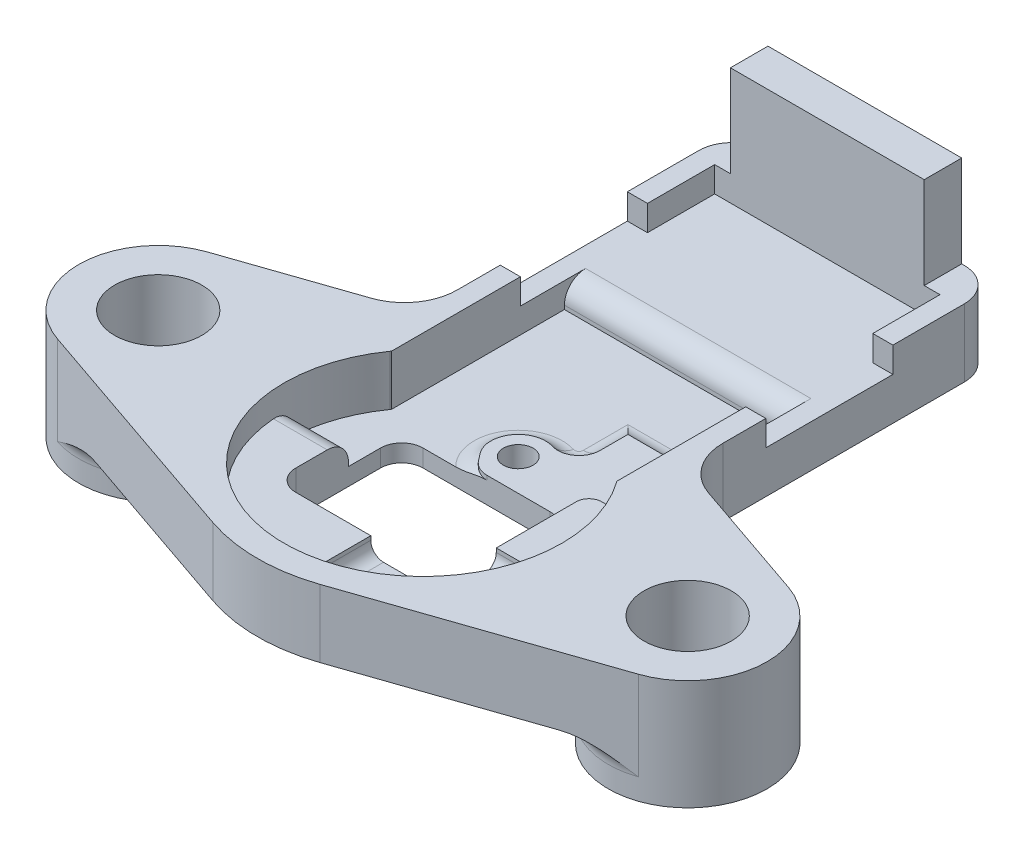
SolidWorks part; units mm, degrees
ref_plane "Front Plane" through (0, 0, 0) normal (0, 0, 1) x (1, 0, 0)
ref_plane "Top Plane" through (0, 0, 0) normal (0, 1, 0) x (1, 0, 0)
ref_plane "Right Plane" through (0, 0, 0) normal (1, 0, 0) x (0, 0, -1)
sketch "Sketch1" plane through (0, 0, 0) normal (0, -1, 0) x (1, 0, 0)
  line L6 (6.3754, -15.4686) -> (6.3754, -6.1404)
  line L7 (-6.3754, -15.4686) -> (6.3754, -15.4686)
  line L8 (-6.3754, -6.1404) -> (-6.3754, -15.4686)
  line L20 (17.4219, 4.5043) -> (3.2216, 9.3809)
  line L21 (-3.2216, 9.3809) -> (-17.4219, 4.5043)
  line L22 (-17.4219, -4.5043) -> (-10.1067, -7.0165)
  line L23 (-7.9629, -10.0193) -> (-7.9629, -14.7701)
  line L24 (-5.6769, -17.0561) -> (5.6769, -17.0561)
  line L25 (7.9629, -14.7701) -> (7.9629, -10.0193)
  line L26 (10.1067, -7.0165) -> (17.4219, -4.5043)
  circle A2 centre (15.875, 0) radius 2.6162
  arc A6 (6.7965, -4.8183) -> (-6.7965, -4.8183) centre (0, 0) ccw
  arc A7 (6.7965, -4.8183) -> (6.3754, -6.1404) centre (8.6614, -6.1404) ccw
  arc A8 (-6.3754, -6.1404) -> (-6.7965, -4.8183) centre (-8.6614, -6.1404) ccw
  circle A10 centre (-15.875, 0) radius 2.6162
  arc A24 (3.2216, 9.3809) -> (-3.2216, 9.3809) centre (0, 0) ccw
  arc A25 (-17.4219, 4.5043) -> (-17.4219, -4.5043) centre (-15.875, 0) ccw
  arc A26 (-7.9629, -10.0193) -> (-10.1067, -7.0165) centre (-11.1379, -10.0193) ccw
  arc A27 (-7.9629, -14.7701) -> (-5.6769, -17.0561) centre (-5.6769, -14.7701) ccw
  arc A28 (5.6769, -17.0561) -> (7.9629, -14.7701) centre (5.6769, -14.7701) ccw
  arc A29 (10.1067, -7.0165) -> (7.9629, -10.0193) centre (11.1379, -10.0193) ccw
  arc A30 (17.4219, -4.5043) -> (17.4219, 4.5043) centre (15.875, 0) ccw
extrude "Boss-Extrude1" add sketch "Sketch1" along normal blind 6.604
sketch "Sketch2" plane through (0, -6.604, 0) normal (0, -1, 0) x (1, 0, 0)
  line L3 (6.3754, -15.4686) -> (6.3754, -6.1404)
  line L4 (-6.3754, -15.4686) -> (6.3754, -15.4686)
  line L5 (-6.3754, -6.1404) -> (-6.3754, -15.4686)
  line L6 (6.3754, -15.4686) -> (6.3754, -6.1404)
  line L7 (-6.3754, -15.4686) -> (6.3754, -15.4686)
  line L8 (-6.3754, -6.1404) -> (-6.3754, -15.4686)
  arc A3 (6.7965, -4.8183) -> (-6.7965, -4.8183) centre (0, 0) ccw
  arc A4 (6.7965, -4.8183) -> (6.3754, -6.1404) centre (8.6614, -6.1404) ccw
  arc A5 (-6.3754, -6.1404) -> (-6.7965, -4.8183) centre (-8.6614, -6.1404) ccw
  arc A6 (6.7965, -4.8183) -> (-6.7965, -4.8183) centre (0, 0) ccw
  arc A7 (6.7965, -4.8183) -> (6.3754, -6.1404) centre (8.6614, -6.1404) ccw
  arc A8 (-6.3754, -6.1404) -> (-6.7965, -4.8183) centre (-8.6614, -6.1404) ccw
  dimension "D1" = 0
extrude "Boss-Extrude2" add sketch "Sketch2" against normal blind 5.08
sketch "Sketch3" plane through (0, -6.604, 0) normal (0, -1, 0) x (1, 0, 0)
  line L7 (17.4219, 4.5043) -> (3.2216, 9.3809)
  line L8 (-3.2216, 9.3809) -> (-17.4219, 4.5043)
  line L9 (-17.4219, -4.5043) -> (-10.1067, -7.0165)
  line L10 (-7.9629, -10.0193) -> (-7.9629, -14.7701)
  line L11 (-5.6769, -17.0561) -> (5.6769, -17.0561)
  line L12 (7.9629, -14.7701) -> (7.9629, -10.0193)
  line L13 (10.1067, -7.0165) -> (17.4219, -4.5043)
  line L14 (17.4219, 4.5043) -> (3.2216, 9.3809)
  line L15 (-3.2216, 9.3809) -> (-17.4219, 4.5043)
  line L16 (-17.4219, -4.5043) -> (-10.1067, -7.0165)
  line L17 (-7.9629, -10.0193) -> (-7.9629, -14.7701)
  line L18 (-5.6769, -17.0561) -> (5.6769, -17.0561)
  line L19 (7.9629, -14.7701) -> (7.9629, -10.0193)
  line L20 (10.1067, -7.0165) -> (17.4219, -4.5043)
  circle A0 centre (-15.875, 0) radius 4.7625
  circle A1 centre (15.875, 0) radius 2.6162
  circle A2 centre (15.875, 0) radius 2.6162
  circle A3 centre (-15.875, 0) radius 2.6162
  circle A4 centre (-15.875, 0) radius 2.6162
  circle A5 centre (15.875, 0) radius 4.7625
  arc A6 (17.4219, -4.5043) -> (17.4219, 4.5043) centre (15.875, 0) ccw construction
  arc A7 (-17.4219, 4.5043) -> (-17.4219, -4.5043) centre (-15.875, 0) ccw construction
  arc A8 (17.4219, -4.5043) -> (17.4219, 4.5043) centre (15.875, 0) ccw
  arc A9 (-17.4219, 4.5043) -> (-17.4219, -4.5043) centre (-15.875, 0) ccw
  arc A17 (17.4219, -4.5043) -> (17.4219, 4.5043) centre (15.875, 0) ccw
  arc A18 (3.2216, 9.3809) -> (-3.2216, 9.3809) centre (0, 0) ccw
  arc A19 (-17.4219, 4.5043) -> (-17.4219, -4.5043) centre (-15.875, 0) ccw
  arc A20 (-7.9629, -10.0193) -> (-10.1067, -7.0165) centre (-11.1379, -10.0193) ccw
  arc A21 (-7.9629, -14.7701) -> (-5.6769, -17.0561) centre (-5.6769, -14.7701) ccw
  arc A22 (5.6769, -17.0561) -> (7.9629, -14.7701) centre (5.6769, -14.7701) ccw
  arc A23 (10.1067, -7.0165) -> (7.9629, -10.0193) centre (11.1379, -10.0193) ccw
  arc A24 (17.4219, -4.5043) -> (17.4219, 4.5043) centre (15.875, 0) ccw
  arc A25 (3.2216, 9.3809) -> (-3.2216, 9.3809) centre (0, 0) ccw
  arc A26 (-17.4219, 4.5043) -> (-17.4219, -4.5043) centre (-15.875, 0) ccw
  arc A27 (-7.9629, -10.0193) -> (-10.1067, -7.0165) centre (-11.1379, -10.0193) ccw
  arc A28 (-7.9629, -14.7701) -> (-5.6769, -17.0561) centre (-5.6769, -14.7701) ccw
  arc A29 (5.6769, -17.0561) -> (7.9629, -14.7701) centre (5.6769, -14.7701) ccw
  arc A30 (10.1067, -7.0165) -> (7.9629, -10.0193) centre (11.1379, -10.0193) ccw
  line M19 (17.4219, 4.5043) -> (3.2216, 9.3809)
  arc M20 (3.2216, 9.3809) -> (-3.2216, 9.3809) centre (0, 0) ccw
  line M21 (-3.2216, 9.3809) -> (-17.4219, 4.5043)
  line M23 (-17.4219, -4.5043) -> (-10.1067, -7.0165)
  arc M24 (-10.1067, -7.0165) -> (-7.9629, -10.0193) centre (-11.1379, -10.0193) cw
  line M25 (-7.9629, -10.0193) -> (-7.9629, -14.7701)
  arc M26 (-7.9629, -14.7701) -> (-5.6769, -17.0561) centre (-5.6769, -14.7701) ccw
  line M27 (-5.6769, -17.0561) -> (5.6769, -17.0561)
  arc M28 (5.6769, -17.0561) -> (7.9629, -14.7701) centre (5.6769, -14.7701) ccw
  line M29 (7.9629, -14.7701) -> (7.9629, -10.0193)
  arc M30 (7.9629, -10.0193) -> (10.1067, -7.0165) centre (11.1379, -10.0193) cw
  line M31 (10.1067, -7.0165) -> (17.4219, -4.5043)
  dimension "D1" = 0
  dimension "D2" = 0
  dimension "D3" = 0
extrude "Cut-Extrude1" cut sketch "Sketch3" against normal blind 2.54 contours A5 A0 M19 M20 M21 M23 M24 M25 M26 M27 M28 M29 M30 M31 region at (0, -6.604, -2.9981)
sketch "Sketch5" plane through (0, -6.604, 0) normal (0, -1, 0) x (1, 0, 0)
  line L0 (-15.875, 0) -> (15.875, 0) construction
  circle A0 centre (0, 0) radius 12.446
  circle A1 centre (15.875, 0) radius 2.6162
  circle A2 centre (15.875, 0) radius 2.6162
  circle A3 centre (-15.875, 0) radius 2.6162
  circle A4 centre (-15.875, 0) radius 2.6162
  dimension "D3" = 24.892
  dimension "D1" = 0
  dimension "D2" = 0
extrude "Cut-Extrude2" cut sketch "Sketch5" against normal blind 1.6002
sketch "Sketch6" plane through (0, -6.604, 0) normal (0, -1, 0) x (1, 0, 0)
  line L0 (-15.875, 0) -> (15.875, 0) construction
  circle A0 centre (0, 0) radius 3.302
  circle A1 centre (15.875, 0) radius 2.6162
  circle A2 centre (15.875, 0) radius 2.6162
  circle A3 centre (-15.875, 0) radius 2.6162
  circle A4 centre (-15.875, 0) radius 2.6162
  dimension "D3" = 6.604
  dimension "D1" = 0
  dimension "D2" = 0
extrude "Cut-Extrude3" cut sketch "Sketch6" against normal through all contours A0
sketch "Sketch8" plane through (0, 0, 0) normal (0, 1, 0) x (1, 0, 0)
  line L0 (-7.9629, 10.0193) -> (-7.9629, 14.7701) construction
  line L1 (-7.9629, 11.8189) -> (7.9629, 11.8189)
  line L2 (-7.9629, 11.8189) -> (-7.9629, 19.6086)
  line L3 (-7.9629, 19.6086) -> (7.9629, 19.6086)
  line L4 (7.9629, 11.8189) -> (7.9629, 19.6086)
extrude "Cut-Extrude4" cut sketch "Sketch8" against normal through all
sketch "Sketch9" plane through (0, 0, -11.8189) normal (0, 0, -1) x (-1, 0, 0)
  line L8 (6.3754, 0) -> (6.3754, -1.524)
  line L9 (6.3754, -1.524) -> (-6.3754, -1.524)
  line L10 (-6.3754, -1.524) -> (-6.3754, 0)
  line L11 (-6.3754, 0) -> (-7.9629, 0)
  line L12 (-7.9629, 0) -> (-7.9629, -4.064)
  line L13 (-7.9629, -4.064) -> (7.9629, -4.064)
  line L14 (7.9629, -4.064) -> (7.9629, 0)
  line L15 (7.9629, 0) -> (6.3754, 0)
  line L16 (6.3754, 0) -> (6.3754, -1.524)
  line L17 (6.3754, -1.524) -> (-6.3754, -1.524)
  line L18 (-6.3754, -1.524) -> (-6.3754, 0)
  line L19 (-6.3754, 0) -> (-7.9629, 0)
  line L20 (-7.9629, 0) -> (-7.9629, -4.064)
  line L21 (-7.9629, -4.064) -> (7.9629, -4.064)
  line L22 (7.9629, -4.064) -> (7.9629, 0)
  line L23 (7.9629, 0) -> (6.3754, 0)
  dimension "D1" = 0
extrude "Boss-Extrude3" add sketch "Sketch9" along normal blind 25.4
sketch "Sketch11" plane through (0, 0, 0) normal (0, 1, 0) x (1, 0, 0)
  line L0 (-7.9629, 10.0193) -> (-7.9629, 37.2189) construction
  line L1 (7.9629, 37.2189) -> (-7.9629, 37.2189)
  line L2 (7.9629, 37.2189) -> (7.9629, 23.5)
  line L3 (7.9629, 23.5) -> (-7.9629, 23.5)
  line L4 (-7.9629, 37.2189) -> (-7.9629, 23.5)
  point P7 (0, 23.5)
  dimension "D1" = 23.5
extrude "Cut-Extrude5" cut sketch "Sketch11" against normal through all
sketch "Sketch12" plane through (0, 0, -23.5) normal (0, 0, -1) x (-1, 0, 0)
  line L1 (-7.9629, 0) -> (7.9629, 0)
  line L2 (-7.9629, 0) -> (-7.9629, -4.064)
  line L3 (-7.9629, -4.064) -> (7.9629, -4.064)
  line L4 (7.9629, 0) -> (7.9629, -4.064)
extrude "Boss-Extrude4" add sketch "Sketch12" along normal blind 2
sketch "Sketch13" plane through (0, -1.524, 0) normal (0, 1, 0) x (1, 0, 0)
  line L0 (0, 0) -> (0, 5.715) construction
  circle A0 centre (0, 5.715) radius 0.889
  dimension "D1" = 1.778
  dimension "D2" = 5.715
extrude "Cut-Extrude6" cut sketch "Sketch13" against normal through all
sketch "Sketch14" plane through (0, 0, 0) normal (0, 1, 0) x (1, 0, 0)
  line L0 (0, 0) -> (0, 15.1) construction
  line L1 (-7.9629, 10.0193) -> (-7.9629, 25.5) construction
  line L2 (-7.9629, 12.6) -> (7.9629, 12.6)
  line L3 (-7.9629, 12.6) -> (-7.9629, 20.22)
  line L4 (-7.9629, 20.22) -> (7.9629, 20.22)
  line L5 (7.9629, 12.6) -> (7.9629, 20.22)
  line L6 (7.9629, 25.5) -> (7.9629, 10.0193) construction
  circle A1 centre (0, 0) radius 3.302
  circle A4 centre (0, 0) radius 3.302 construction
  line M5 (7.9629, 10.0193) -> (7.9629, 25.5)
  line M7 (-7.9629, 25.5) -> (-7.9629, 10.0193)
  line M18 (6.3754, 23.5) -> (6.3754, 6.1404)
  line M22 (-6.3754, 6.1404) -> (-6.3754, 23.5)
  dimension "D2" = 15.1
  dimension "D3" = 2.5
  dimension "D4" = 7.62
  dimension "D1" = 0
extrude "Cut-Extrude8" cut sketch "Sketch14" against normal up to surface (1.524 mm away) contours L4 L2 M22 M18 | L4 L2 M7 M22 | L4 L2 M18 M5 region at (-7.1691, 0, -16.41) region at (0, 0, -16.41) region at (7.1692, 0, -16.41) up to face at (0, -1.524, -4.826)
sketch "Sketch15" plane through (0, -1.524, 0) normal (0, 1, 0) x (1, 0, 0)
  line L1 (5.08, 3.81) -> (-5.08, 3.81)
  line L2 (5.08, 3.81) -> (5.08, -3.81)
  line L3 (5.08, -3.81) -> (-5.08, -3.81)
  line L4 (-5.08, 3.81) -> (-5.08, -3.81)
  line L5 (5.08, 3.81) -> (-5.08, -3.81) construction
  line L6 (5.08, -3.81) -> (-5.08, 3.81) construction
  point P0 (0, 0)
  dimension "D1" = 7.62
  dimension "D2" = 10.16
extrude "Cut-Extrude9" cut sketch "Sketch15" against normal through all
sketch "Sketch19" plane through (0, 0, 0) normal (0, 1, 0) x (1, 0, 0)
  line L0 (-6.3754, 23.5) -> (6.3754, 23.5) construction
  line L1 (6.7564, 2.54) -> (-6.7564, 2.54)
  line L2 (6.7564, 2.54) -> (6.7564, 23.5)
  line L3 (6.7564, 23.5) -> (-6.7564, 23.5)
  line L4 (-6.7564, 2.54) -> (-6.7564, 23.5)
  line L5 (-6.3754, 6.1404) -> (-6.3754, 12.6) construction
  point P6 (0, 2.54)
  dimension "D1" = 0.381
  dimension "D2" = 2.54
extrude "Cut-Extrude13" cut sketch "Sketch19" against normal up to surface (1.524 mm away) up to face at (0, -1.524, 0)
sketch "Sketch16" plane through (0, -1.524, 0) normal (0, 1, 0) x (1, 0, 0)
  line L0 (5.08, 3.81) -> (-5.08, 3.81) construction
  line L1 (-6.7564, 3.81) -> (2.1336, 3.81)
  line L2 (-6.7564, 3.81) -> (-6.7564, 15.24)
  line L3 (-6.7564, 15.24) -> (2.1336, 15.24)
  line L4 (2.1336, 3.81) -> (2.1336, 15.24)
  line L8 (2.1336, 15.24) -> (6.7564, 15.24)
  line L9 (2.1336, 15.24) -> (2.1336, 10.16)
  line L10 (2.1336, 10.16) -> (6.7564, 10.16)
  line L11 (6.7564, 15.24) -> (6.7564, 10.16)
  line L12 (-6.7564, 12.6) -> (-6.7564, 4.8768) construction
  line L13 (6.7564, 4.8768) -> (6.7564, 12.6) construction
  line M7 (-5.08, 3.81) -> (5.08, 3.81)
  circle M9 centre (0, 5.715) radius 0.889
  dimension "D1" = 8.89
  dimension "D2" = 11.43
  dimension "D3" = 5.08
extrude "Cut-Extrude10" cut sketch "Sketch16" against normal blind 1.5 contours L4 L3 L2 L1 M7 M9 | L11 L8 L4 L10 region at (-2.3693, -1.524, -9.6204) region at (4.445, -1.524, -12.7)
sketch "Sketch18" plane through (0, -1.524, 0) normal (0, 1, 0) x (1, 0, 0)
  line L1 (2.1336, 10.16) -> (6.7564, 10.16)
  line L2 (2.1336, 10.16) -> (2.1336, 4.8768)
  line L3 (2.1336, 4.8768) -> (6.7564, 4.8768)
  line L4 (6.7564, 10.16) -> (6.7564, 4.8768)
  line L5 (6.7564, 4.8768) -> (6.7564, 10.16) construction
  line L6 (5.08, 4.8768) -> (5.08, 3.81)
  line L7 (5.08, 3.81) -> (2.1336, 3.81)
  line L8 (2.1336, 3.81) -> (2.1336, 4.8768)
  arc A0 (6.7564, 4.8768) -> (6.7965, 4.8183) centre (8.6614, 6.1404) ccw construction
  line M7 (6.7564, 10.16) -> (2.1336, 10.16)
  line M8 (2.1336, 10.16) -> (2.1336, 3.81)
  line M9 (2.1336, 3.81) -> (5.08, 3.81)
  line M15 (6.7564, 4.8768) -> (6.7564, 10.16)
extrude "Cut-Extrude12" cut sketch "Sketch18" against normal blind 1 contours L6 L3 M8 M9 | L3 M8 M15 M7 region at (4.445, -1.524, -7.5184) region at (3.6068, -1.524, -4.3434)
sketch "Sketch20" plane through (0, 0, 0) normal (0, 1, 0) x (1, 0, 0)
  line L0 (-6.7564, 23.5) -> (-6.7564, 20.22) construction
  line L1 (6.7564, 23.5) -> (-6.7564, 23.5)
  line L2 (6.7564, 23.5) -> (6.7564, 24.25)
  line L3 (6.7564, 24.25) -> (-6.7564, 24.25)
  line L4 (-6.7564, 23.5) -> (-6.7564, 24.25)
  dimension "D1" = 0.75
extrude "Cut-Extrude14" cut sketch "Sketch20" against normal up to surface (1.524 mm away) up to face at (0, -1.524, -17.3967)
sketch "Sketch21" plane through (0, -1.524, 0) normal (0, 1, 0) x (1, 0, 0)
  line L0 (0.6831, -8.3031) -> (0.6831, -0.6831)
  line L1 (0.6831, -0.6831) -> (8.3031, -0.6831)
  arc A1 (-6.7965, 4.8183) -> (6.7965, 4.8183) centre (0, 0) ccw construction
  arc A2 (-6.7965, 4.8183) -> (6.7965, 4.8183) centre (0, 0) ccw construction
  arc A3 (-6.7965, 4.8183) -> (6.7965, 4.8183) centre (0, 0) ccw
  line M3 (5.08, 4.8768) -> (5.08, -3.81)
  line M4 (5.08, -3.81) -> (-5.08, -3.81)
  arc M9 (-6.7965, 4.8183) -> (6.7965, 4.8183) centre (0, 0) ccw
  dimension "D1" = 7.62
  dimension "D2" = 7.62
extrude "Cut-Extrude16" cut sketch "Sketch21" against normal blind 1 contours L1 L0 M3 M4 M9 region at (4.2763, -1.524, 4.5687)
sketch "Sketch23" plane through (0, -1.524, 0) normal (0, 1, 0) x (1, 0, 0)
  line L0 (-5.08, 0.6122) -> (-8.3087, 0.6122)
  line L1 (-5.08, 3.81) -> (-5.08, -3.81) construction
  line L2 (-6.7564, 3.81) -> (-6.7564, 4.8768) construction
  line L3 (-6.7564, 3.81) -> (-5.08, 3.81) construction
  line L4 (-6.7564, 3.81) -> (-6.7564, 4.8768)
  line L5 (-6.7564, 3.81) -> (-5.08, 3.81)
  line L6 (-5.08, 3.81) -> (-5.08, -3.81)
  arc A0 (-6.7965, 4.8183) -> (0.6831, -8.3031) centre (0, 0) ccw construction
  arc A1 (-6.7965, 4.8183) -> (0.6831, -8.3031) centre (0, 0) ccw
  line M3 (-5.08, -3.81) -> (-5.08, 3.81)
  line M4 (-5.08, 3.81) -> (-6.7564, 3.81)
  line M5 (-6.7564, 3.81) -> (-6.7564, 4.8768)
  arc M6 (-6.7564, 4.8768) -> (-6.7965, 4.8183) centre (-8.6614, 6.1404) cw
  arc M7 (-6.7965, 4.8183) -> (0.6831, -8.3031) centre (0, 0) ccw
extrude "Cut-Extrude17" cut sketch "Sketch23" against normal up to surface (1.5 mm away) contours L0 M3 M4 M5 M6 M7 region at (-6.5562, -1.524, -2.207) up to face at (0, -3.024, -4.826)
sketch "Sketch24" plane through (0, -3.024, 0) normal (0, 1, 0) x (1, 0, 0)
  line L0 (0.8077, 7.1412) -> (2.1336, 6.3903)
  line L1 (2.1336, 3.81) -> (2.1336, 10.16) construction
  line L2 (-1.1774, 4.5748) -> (-0.6057, 3.81)
  line L3 (-5.08, 3.81) -> (2.1336, 3.81) construction
  line L4 (-0.6057, 3.81) -> (2.1336, 3.81)
  line L5 (2.1336, 3.81) -> (2.1336, 6.3903)
  circle A0 centre (0, 5.715) radius 1.639
  circle A1 centre (0, 5.715) radius 0.889 construction
  line M6 (-5.08, 3.81) -> (2.1336, 3.81)
  line M7 (2.1336, 3.81) -> (2.1336, 10.16)
  circle M11 centre (0, 5.715) radius 0.889
  dimension "D1" = 0.75
extrude "Boss-Extrude5" add sketch "Sketch24" along normal up to surface (0.5 mm away) contours A0 L2 L0 M6 M7 | A0 M11 region at (1.4475, -3.024, -6.7249) region at (1.3759, -3.024, -6.517) up to face at (4.6567, -2.524, -6.2823)
sketch "Sketch25" plane through (0, 0, 0) normal (0, 1, 0) x (1, 0, 0)
  line L18 (-6.7564, 20.22) -> (-6.7564, 24.25)
  line L19 (-6.7564, 24.25) -> (6.7564, 24.25)
  line L20 (-6.7564, 4.8768) -> (-6.7564, 12.6)
  line L21 (-6.7564, 12.6) -> (-7.9629, 12.6)
  line L22 (-7.9629, 12.6) -> (-7.9629, 10.0193)
  line L23 (-10.1067, 7.0165) -> (-17.4219, 4.5043)
  line L24 (-17.4219, -4.5043) -> (-3.2216, -9.3809)
  line L25 (3.2216, -9.3809) -> (17.4219, -4.5043)
  line L26 (17.4219, 4.5043) -> (10.1067, 7.0165)
  line L27 (7.9629, 10.0193) -> (7.9629, 12.6)
  line L28 (7.9629, 12.6) -> (6.7564, 12.6)
  line L29 (6.7564, 12.6) -> (6.7564, 4.8768)
  line L30 (-6.7564, 4.8768) -> (-6.7564, 12.6)
  line L31 (-6.7564, 12.6) -> (-7.9629, 12.6)
  line L32 (-7.9629, 12.6) -> (-7.9629, 10.0193)
  line L33 (-10.1067, 7.0165) -> (-17.4219, 4.5043)
  line L34 (-17.4219, -4.5043) -> (-3.2216, -9.3809)
  line L35 (3.2216, -9.3809) -> (17.4219, -4.5043)
  line L36 (17.4219, 4.5043) -> (10.1067, 7.0165)
  line L37 (7.9629, 10.0193) -> (7.9629, 12.6)
  line L38 (7.9629, 12.6) -> (6.7564, 12.6)
  line L39 (6.7564, 12.6) -> (6.7564, 4.8768)
  line L40 (6.7564, 24.25) -> (6.7564, 20.22)
  line L41 (6.7564, 20.22) -> (7.9629, 20.22)
  line L42 (7.9629, 20.22) -> (7.9629, 25.5)
  line L43 (7.9629, 25.5) -> (-7.9629, 25.5)
  line L44 (-7.9629, 25.5) -> (-7.9629, 20.22)
  line L45 (-7.9629, 20.22) -> (-6.7564, 20.22)
  line L46 (-6.7564, 20.22) -> (-6.7564, 24.25)
  line L47 (-6.7564, 24.25) -> (6.7564, 24.25)
  line L48 (6.7564, 24.25) -> (6.7564, 20.22)
  line L49 (6.7564, 20.22) -> (7.9629, 20.22)
  line L50 (7.9629, 20.22) -> (7.9629, 25.5)
  line L51 (7.9629, 25.5) -> (-7.9629, 25.5)
  line L52 (-7.9629, 25.5) -> (-7.9629, 20.22)
  line L53 (-7.9629, 20.22) -> (-6.7564, 20.22)
  circle A9 centre (15.875, 0) radius 2.6162
  circle A10 centre (15.875, 0) radius 2.6162
  circle A11 centre (-15.875, 0) radius 2.6162
  circle A12 centre (-15.875, 0) radius 2.6162
  arc A20 (-6.7965, 4.8183) -> (-6.7564, 4.8768) centre (-8.6614, 6.1404) ccw
  arc A21 (-10.1067, 7.0165) -> (-7.9629, 10.0193) centre (-11.1379, 10.0193) ccw
  arc A22 (-17.4219, 4.5043) -> (-17.4219, -4.5043) centre (-15.875, 0) ccw
  arc A23 (-3.2216, -9.3809) -> (3.2216, -9.3809) centre (0, 0) ccw
  arc A24 (17.4219, -4.5043) -> (17.4219, 4.5043) centre (15.875, 0) ccw
  arc A25 (7.9629, 10.0193) -> (10.1067, 7.0165) centre (11.1379, 10.0193) ccw
  arc A26 (6.7564, 4.8768) -> (6.7965, 4.8183) centre (8.6614, 6.1404) ccw
  arc A27 (-6.7965, 4.8183) -> (6.7965, 4.8183) centre (0, 0) ccw
  arc A28 (-6.7965, 4.8183) -> (-6.7564, 4.8768) centre (-8.6614, 6.1404) ccw
  arc A29 (-10.1067, 7.0165) -> (-7.9629, 10.0193) centre (-11.1379, 10.0193) ccw
  arc A30 (-17.4219, 4.5043) -> (-17.4219, -4.5043) centre (-15.875, 0) ccw
  arc A31 (-3.2216, -9.3809) -> (3.2216, -9.3809) centre (0, 0) ccw
  arc A32 (17.4219, -4.5043) -> (17.4219, 4.5043) centre (15.875, 0) ccw
  arc A33 (7.9629, 10.0193) -> (10.1067, 7.0165) centre (11.1379, 10.0193) ccw
  arc A34 (6.7564, 4.8768) -> (6.7965, 4.8183) centre (8.6614, 6.1404) ccw
  arc A35 (-6.7965, 4.8183) -> (6.7965, 4.8183) centre (0, 0) ccw
  dimension "D1" = 0
  dimension "D2" = 0
  dimension "D3" = 0
  dimension "D4" = 0
fillet "Fillet3" radius 1.27 2 edges at (11.1125, -4.064, 0) (-11.1125, -4.064, 0)
fillet "Fillet4" radius 1.27 4 edges at (-5.08, -3.544, -3.81) (-5.08, -2.794, 3.81) (5.08, -3.294, 3.81) (5.08, -3.294, -3.81)
fillet "Fillet5" radius 1.27 1 edges at (2.1336, -2.774, -6.3903)
fillet "Fillet6" radius 1.27 1 edges at (-0.6057, -2.774, -3.81)
fillet "Fillet7" radius 1.27 3 edges at (2.1336, -3.024, -9.3264) (1.6166, -3.024, -7.4702) (-1.3961, -3.024, -6.5737)
fillet "Fillet8" radius 1.27 1 edges at (3.94, -3.024, -10.16)
fillet "Fillet9" radius 0.762 2 edges at (0.6831, -2.524, 6.0566) (6.6916, -2.524, 0.6831)
fillet "Fillet10" radius 0.762 1 edges at (5.08, -2.024, -4.8768)
fillet "Fillet11" radius 1.27 1 edges at (0, -1.524, -15.24)
fillet "Fillet12" radius 1.27 1 edges at (-6.6943, -1.524, -0.6122)
sketch "Sketch26" plane through (0, 0, 0) normal (0, 1, 0) x (1, 0, 0)
  line L0 (0, 24.25) -> (0, 25.5) construction
  line L2 (5.81, 24.25) -> (-5.81, 24.25)
  line L3 (5.81, 24.25) -> (5.81, 25.5)
  line L4 (5.81, 25.5) -> (-5.81, 25.5)
  line L5 (-5.81, 24.25) -> (-5.81, 25.5)
  line L8 (-6.7564, 20.22) -> (-6.7564, 24.25)
  line L9 (-6.7564, 24.25) -> (6.7564, 24.25)
  line L10 (6.7564, 24.25) -> (6.7564, 20.22)
  line L11 (6.7564, 20.22) -> (7.9629, 20.22)
  line L12 (7.9629, 20.22) -> (7.9629, 25.5)
  line L13 (7.9629, 25.5) -> (-7.9629, 25.5)
  line L14 (-7.9629, 25.5) -> (-7.9629, 20.22)
  line L15 (-7.9629, 20.22) -> (-6.7564, 20.22)
  line L16 (-6.7564, 20.22) -> (-6.7564, 24.25) construction
  line L17 (-6.7564, 24.25) -> (6.7564, 24.25) construction
  line L18 (6.7564, 24.25) -> (6.7564, 20.22) construction
  line L19 (6.7564, 20.22) -> (7.9629, 20.22) construction
  line L20 (7.9629, 20.22) -> (7.9629, 25.5) construction
  line L21 (7.9629, 25.5) -> (-7.9629, 25.5) construction
  line L22 (-7.9629, 25.5) -> (-7.9629, 20.22) construction
  line L23 (-7.9629, 20.22) -> (-6.7564, 20.22) construction
  point P14 (-4.0459, 24.25)
  point P15 (0, 24.25)
  dimension "D2" = 11.62
  dimension "D1" = 0
extrude "Boss-Extrude6" add sketch "Sketch26" along normal blind 5.5
sketch "Sketch28" plane through (0, 0, -25.5) normal (0, 0, -1) x (-1, 0, 0)
  line L8 (-7.9629, 0) -> (-7.9629, -4.064)
  line L9 (-7.9629, -4.064) -> (7.9629, -4.064)
  line L10 (7.9629, -4.064) -> (7.9629, 0)
  line L11 (7.9629, 0) -> (5.81, 0)
  line L12 (5.81, 0) -> (5.81, 5.5)
  line L13 (5.81, 5.5) -> (-5.81, 5.5)
  line L14 (-5.81, 5.5) -> (-5.81, 0)
  line L15 (-5.81, 0) -> (-7.9629, 0)
  line L16 (-7.9629, 0) -> (-7.9629, -4.064)
  line L17 (-7.9629, -4.064) -> (7.9629, -4.064)
  line L18 (7.9629, -4.064) -> (7.9629, 0)
  line L19 (7.9629, 0) -> (5.81, 0)
  line L20 (5.81, 0) -> (5.81, 5.5)
  line L21 (5.81, 5.5) -> (-5.81, 5.5)
  line L22 (-5.81, 5.5) -> (-5.81, 0)
  line L23 (-5.81, 0) -> (-7.9629, 0)
  dimension "D1" = 0
extrude "Boss-Extrude7" add sketch "Sketch28" along normal blind 1
fillet "Fillet13" radius 2 2 edges at (7.9629, -2.032, -26.5) (-7.9629, -2.032, -26.5)
